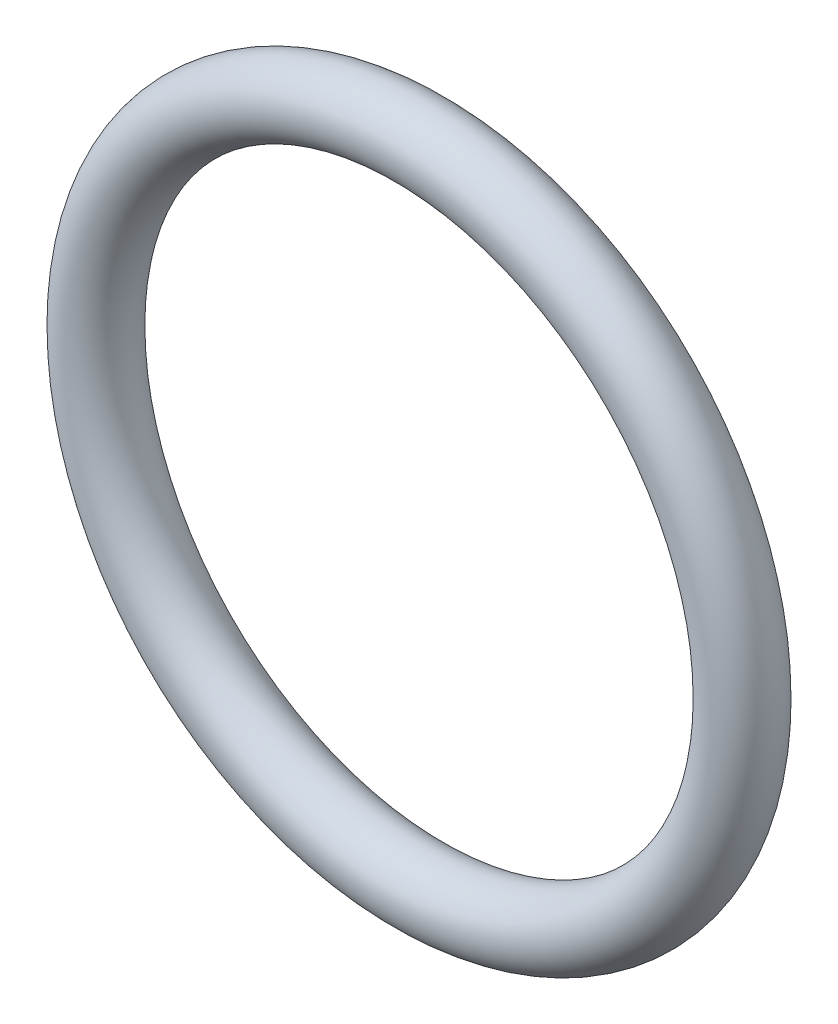
SolidWorks part; units mm, degrees
material "Silicon"
ref_plane "Front Plane" through (0, 0, 0) normal (0, 0, 1) x (1, 0, 0)
ref_plane "Top Plane" through (0, 0, 0) normal (0, 1, 0) x (1, 0, 0)
ref_plane "Right Plane" through (0, 0, 0) normal (1, 0, 0) x (0, 0, -1)
sketch "Sketch1" plane through (0, 0, 0) normal (0, 0, 1) x (1, 0, 0)
  line L0 (0, 0) -> (12.5, 0) construction
  line L1 (12.5, 0) -> (15.5, 0) construction
  circle A0 centre (0, 0) radius 15.5 construction
  circle A1 centre (0, 0) radius 12.5 construction
  point P4 (14, 0)
  dimension "OD" = 31
  dimension "ID" = 25
  dimension "Width" = 3
sketch "Sketch2" plane through (0, 0, 0) normal (0, 1, 0) x (1, 0, 0)
  line L0 (12.5, 0) -> (15.5, 0) construction
  line L4 (0, -6.25) -> (0, 6.25) construction
  line L5 (0, 0) -> (12.5, 0) construction
  line L6 (14, -1.5) -> (14, 1.5) construction
  circle A0 centre (14, 0) radius 1.5
  point P6 (15.5, 0)
  point P11 (0, 0)
  point P16 (14, 0)
revolve "Revolve1" add sketch "Sketch2" angle 360 about L4
ref_axis "Center Axis 1" through (0, 0, -0.55) along (0, 0, 1)
ref_plane "Contact Plane 1" through (14, 0, 1.5) normal (0, 0, 1) x (1, 0, 0)
ref_plane "Contact Plane 2" through (14, 0, -1.5) normal (0, 0, -1) x (-1, 0, 0)
